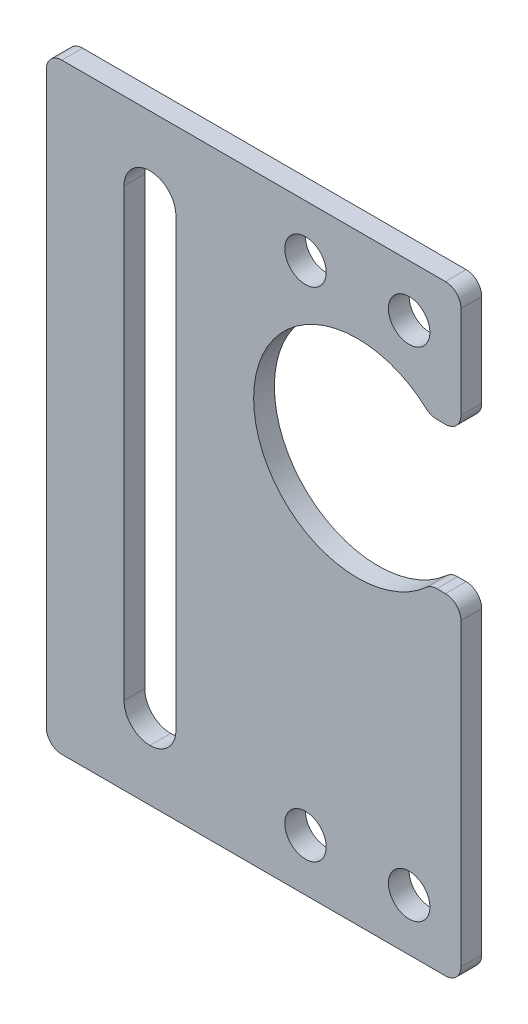
SolidWorks part; units mm, degrees
ref_plane "前视基准面" through (0, 0, 0) normal (0, 0, 1) x (1, 0, 0)
ref_plane "上视基准面" through (0, 0, 0) normal (0, 1, 0) x (1, 0, 0)
ref_plane "右视基准面" through (0, 0, 0) normal (1, 0, 0) x (0, 0, -1)
sketch "草图1" plane through (0, 0, 0) normal (0, 0, 1) x (1, 0, 0)
  line L0 (-20, 24) -> (-17.5, 24)
  line L5 (7.0711, 17.0711) -> (10, 17.0711)
  line L6 (10, 29) -> (10, 17.0711)
  line L11 (-17.5, 24) -> (-17.5, -24)
  line L12 (7.0711, 2.9289) -> (10, 2.9289)
  line L13 (-15, -29) -> (10, -29)
  line L15 (-15, 29) -> (10, 29)
  line L17 (10, 2.9289) -> (10, -29)
  line L18 (-15, 29) -> (-30, 29)
  line L19 (-30, 29) -> (-30, -29)
  line L20 (-30, -29) -> (-15, -29)
  line L22 (-17.5, -24) -> (-22.5, -24)
  line L23 (-22.5, -24) -> (-22.5, 24)
  line L24 (-22.5, 24) -> (-20, 24)
  circle A1 centre (5, -24) radius 2
  circle A2 centre (-5, -24) radius 2
  circle A3 centre (-5, 24) radius 2
  circle A4 centre (5, 24) radius 2
  arc A5 (7.0711, 17.0711) -> (7.0711, 2.9289) centre (0, 10) ccw
  point P0 (0, 0)
  point P10 (0, 0)
  point P15 (0, 0)
extrude "凸台-拉伸1" add sketch "草图1" along normal blind 2
fillet "圆角1" radius 1.5 8 edges at (-30, 29, 1) (-30, -29, 1) (10, -29, 1) (7.0711, 17.0711, 1) (7.0711, 2.9289, 1) (10, 2.9289, 1) (10, 17.0711, 1) (10, 29, 1)
fillet "圆角2" radius 2.5 4 edges at (-17.5, -24, 1) (-22.5, -24, 1) (-22.5, 24, 1) (-17.5, 24, 1)
